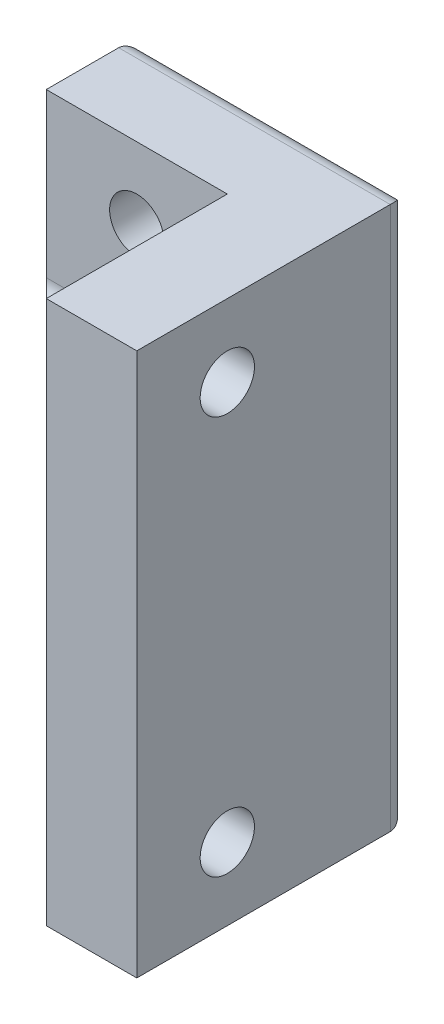
SolidWorks part; units mm, degrees
ref_plane "前基準面" through (0, 0, 0) normal (0, 0, 1) x (1, 0, 0)
ref_plane "上基準面" through (0, 0, 0) normal (0, 1, 0) x (1, 0, 0)
ref_plane "右基準面" through (0, 0, 0) normal (1, 0, 0) x (0, 0, -1)
sketch "草圖1" plane through (0, 0, 0) normal (0, 0, 1) x (1, 0, 0)
  line L1 (-5, 15) -> (5, 15)
  line L2 (-5, 15) -> (-5, -15)
  line L3 (-5, -15) -> (5, -15)
  line L4 (5, 15) -> (5, -15)
  line L5 (-5, 15) -> (5, -15) construction
  line L6 (-5, -15) -> (5, 15) construction
  point P0 (0, 0)
  dimension "D1" = 30
  dimension "D2" = 10
extrude "填料-伸長1" add sketch "草圖1" along normal blind 5
sketch "草圖2" plane through (5, 0, 0) normal (1, 0, 0) x (0, 0, -1)
  line L1 (0, 15) -> (-15, 15)
  line L2 (0, 15) -> (0, -15)
  line L3 (0, -15) -> (-15, -15)
  line L4 (-15, 15) -> (-15, -15)
  dimension "D1" = 15
extrude "填料-伸長2" add sketch "草圖2" along normal blind 5
sketch "草圖3" plane through (5, 0, 0) normal (-1, 0, 0) x (0, 0, 1)
  line L0 (10, 11) -> (10, -11) construction
  line L1 (0, 0) -> (10, 0) construction
  circle A0 centre (10, 11) radius 1.5
  circle A1 centre (10, -11) radius 1.5
  dimension "D1" = 3
  dimension "D2" = 3
  dimension "D3" = 22
  dimension "D4" = 10
sketch "草圖4" plane through (0, 0, 5) normal (0, 0, 1) x (1, 0, 0)
  line L0 (0, -11) -> (0, 11) construction
  circle A0 centre (0, 11) radius 1.5
  circle A1 centre (0, -11) radius 1.5
  dimension "D2" = 3
  dimension "D3" = 3
  dimension "D1" = 22
extrude "除料-伸長1" cut sketch "草圖4" against normal through all
ref_plane "平面1" through (0, 0, 0) normal (0, -1, 0) x (1, 0, 0)
sketch "草圖5" plane through (0, 0, 0) normal (0, -1, 0) x (1, 0, 0)
  line L0 (5, 15) -> (-5, 5)
  line L1 (-5, 5) -> (5, 5)
  line L2 (5, 5) -> (5, 15)
extrude "填料-伸長3" add sketch "草圖5" along normal blind 5 and the other way blind 5
extrude "除料-伸長2" cut sketch "草圖3" against normal blind 5
fillet "圓角1" radius 1 6 edges at (-5, 0, 0) (2.5, -15, 0) (10, 0, 0) (2.5, 15, 0) (1.5, 11, 0) (1.5, -11, 0)
fillet "圓角2" radius 1 4 edges at (0, -5, 5) (5, -5, 10) (0, 5, 5) (5, 5, 10)
